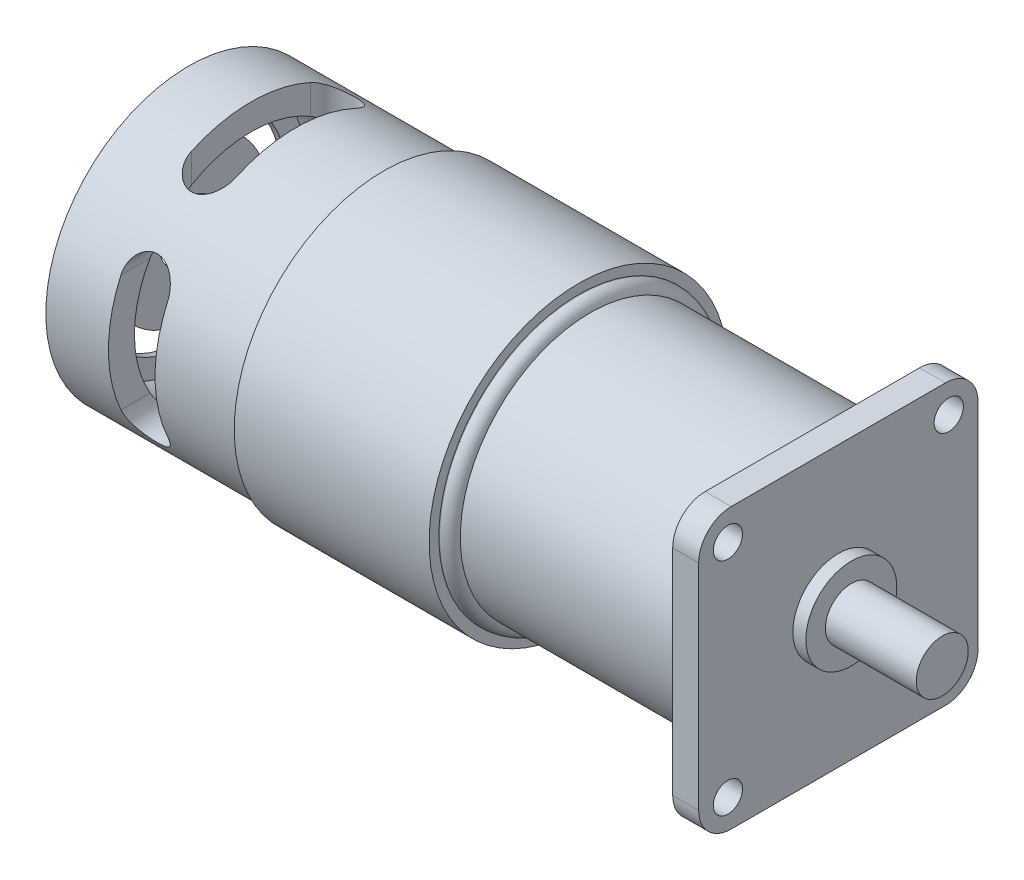
SolidWorks part; units mm, degrees
ref_plane "前视基准面" through (0, 0, 0) normal (0, 0, 1) x (1, 0, 0)
ref_plane "上视基准面" through (0, 0, 0) normal (0, 1, 0) x (1, 0, 0)
ref_plane "右视基准面" through (0, 0, 0) normal (1, 0, 0) x (0, 0, -1)
sketch "草图1" plane through (0, 0, 0) normal (0, 0, 1) x (1, 0, 0)
  line L7 (96, 20) -> (60, 20)
  line L8 (60, 20) -> (60, 23)
  line L9 (60, 23) -> (30, 23)
  line L10 (30, 23) -> (30, 22)
  line L11 (30, 22) -> (0, 22)
  line L12 (0, 22) -> (0, 0)
  line L13 (96, 20) -> (96, 0)
  line L14 (96, 0) -> (0, 0)
  dimension "D1" = 30
  dimension "D2" = 1
  dimension "D3" = 20
  dimension "D4" = 30
  dimension "D5" = 3
  dimension "D6" = 96
revolve "旋转1" add sketch "草图1" angle 360 about L14
sketch "草图2" plane through (0, 0, 0) normal (0, 0, 1) x (1, 0, 0)
  line L0 (96, 0) -> (96, 7)
  line L1 (96, -20) -> (96, 20) construction
  line L2 (96, 7) -> (102, 7)
  line L3 (102, 7) -> (102, 4)
  line L4 (102, 4) -> (116, 4)
  line L5 (116, 4) -> (116, 0)
  line L6 (116, 0) -> (96, 0)
  dimension "D1" = 6
  dimension "D2" = 20
  dimension "D3" = 7
  dimension "D4" = 4
revolve "旋转2" add sketch "草图2" angle 360 about L6
sketch "草图11" plane through (96, 0, 0) normal (1, 0, 0) x (0, 0, -1)
  line L1 (-21.5, 21.5) -> (21.5, 21.5)
  line L2 (-21.5, 21.5) -> (-21.5, -21.5)
  line L3 (-21.5, -21.5) -> (21.5, -21.5)
  line L4 (21.5, 21.5) -> (21.5, -21.5)
  line L5 (-21.5, 21.5) -> (21.5, -21.5) construction
  line L6 (-21.5, -21.5) -> (21.5, 21.5) construction
  point P0 (0, 0)
  dimension "D1" = 43
  dimension "D2" = 43
extrude "凸台-拉伸4" add sketch "草图11" along normal blind 4 separate body
sketch "草图12" plane through (0, 0, 0) normal (-1, 0, 0) x (0, 0, 1)
  circle A0 centre (0, 0) radius 18
  dimension "D1" = 36
extrude "切除-拉伸1" cut sketch "草图12" against normal blind 60
sketch "草图13" plane through (60, 0, 0) normal (-1, 0, 0) x (0, 0, 1)
  circle A0 centre (0, 0) radius 4
  dimension "D1" = 8
extrude "凸台-拉伸5" add sketch "草图13" along normal blind 62
sketch "草图14" plane through (0, 0, 0) normal (-1, 0, 0) x (0, 0, 1)
  circle A0 centre (0, 0) radius 20
  dimension "D1" = 40
extrude "凸台-拉伸6" add sketch "草图14" along normal blind 1
fillet "圆角1" radius 0.5 1 edges at (-1, 0, 20)
ref_axis "基准轴1" through (-29.822, 0, 0) along (1, 0, 0)
sketch "草图17" plane through (-1, 0, 0) normal (-1, 0, 0) x (0, 0, 1)
  arc A0 (-13.4771, 0) -> (0, 13.4771) centre (0, 0) cw construction
  arc A1 (0, 15.0897) -> (-15.0897, 0) centre (0, 0) ccw
  arc A2 (0, 11.8644) -> (-11.8644, 0) centre (0, 0) ccw
  arc A3 (0, 11.8644) -> (0, 15.0897) centre (0, 13.4771) ccw
  arc A4 (-15.0897, 0) -> (-11.8644, 0) centre (-13.4771, 0) ccw
  arc A5 (13.4771, 0) -> (0, -13.4771) centre (0, 0) cw construction
  arc A6 (0, -15.0897) -> (15.0897, 0) centre (0, 0) ccw
  arc A7 (0, -11.8644) -> (11.8644, 0) centre (0, 0) ccw
  arc A8 (0, -11.8644) -> (0, -15.0897) centre (0, -13.4771) ccw
  arc A9 (15.0897, 0) -> (11.8644, 0) centre (13.4771, 0) ccw
  point P4 (-9.5297, 9.5297)
  point P14 (9.5297, -9.5297)
  point P19 (0, 0)
  dimension "D1" = 2
extrude "切除-拉伸6" cut sketch "草图17" against normal blind 10
sketch "草图19" plane through (-2, 0, 0) normal (-1, 0, 0) x (0, 0, 1)
  circle A0 centre (0, 0) radius 1.7291
extrude "凸台-拉伸9" add sketch "草图19" along normal blind 2
fillet "圆角2" radius 1.7 1 edges at (-4, 0, 1.7291)
sketch "草图20" plane through (-1, 0, 0) normal (-1, 0, 0) x (0, 0, 1)
  circle A0 centre (0, 0) radius 4.5
  dimension "D1" = 9
extrude "切除-拉伸9" cut sketch "草图20" against normal blind 2
sketch "草图21" plane through (60, 0, 0) normal (1, 0, 0) x (0, 0, -1)
  circle A0 centre (0, 0) radius 21.5
  dimension "D1" = 43
extrude "凸台-拉伸10" add sketch "草图21" along normal blind 1.8
fillet "圆角3" radius 1.7 1 edges at (61.8, 0, -21.5)
sketch "草图24"
ref_plane "基准面1" through (0, 0, 0) normal (0, 0, -1) x (1, 0, 0)
ref_plane "基准面2" through (0, 0, 22) normal (0, 0, 1) x (1, 0, 0)
sketch "草图45" plane through (0, 0, 0) normal (0, 0, -1) x (1, 0, 0)
  line L0 (13.2288, -8.995) -> (13.2288, 8.995) construction
  line L1 (9.6389, -8.995) -> (9.6389, 8.995)
  line L2 (16.8187, -8.995) -> (16.8187, 8.995)
  arc A0 (9.6389, -8.995) -> (16.8187, -8.995) centre (13.2288, -8.995) ccw
  arc A1 (16.8187, 8.995) -> (9.6389, 8.995) centre (13.2288, 8.995) ccw
  point P2 (13.2288, 0)
extrude "切除-拉伸10" cut sketch "草图45" against normal through all both and the other way through all
ref_plane "基准面3" through (0, 22, 0) normal (0, 1, 0) x (1, 0, 0)
sketch "草图46" plane through (0, 22, 0) normal (0, 1, 0) x (1, 0, 0)
  line L0 (13.0327, -9.1644) -> (13.0327, 9.1644) construction
  line L1 (23.1, 0) -> (-23.1, 0) construction
  line L2 (9.5875, -9.1644) -> (9.5875, 9.1644)
  line L3 (16.478, -9.1644) -> (16.478, 9.1644)
  arc A0 (9.5875, -9.1644) -> (16.478, -9.1644) centre (13.0327, -9.1644) ccw
  arc A1 (16.478, 9.1644) -> (9.5875, 9.1644) centre (13.0327, 9.1644) ccw
  point P4 (13.0327, 0)
extrude "切除-拉伸11" cut sketch "草图46" against normal through all both and the other way through all
sketch "草图48" plane through (16.8187, 0, 0) normal (-1, 0, 0) x (0, 0, 1)
  circle A0 centre (0, 0) radius 4
extrude "凸台-拉伸11" add sketch "草图48" along normal blind 18.5
sketch "草图49" plane through (100, 0, 0) normal (1, 0, 0) x (0, 0, -1)
  line L0 (21.5, 21.5) -> (-21.5, 21.5) construction
  line L1 (-21.5, 21.5) -> (-21.5, -21.5) construction
  circle A0 centre (-17, 17) radius 2.25
  dimension "D1" = 4.5
  dimension "D2" = 4.5
  dimension "D3" = 4.5
extrude "切除-拉伸12" cut sketch "草图49" against normal blind 18.5
mirror "镜向1" about plane through (0, 0, 0) normal (0, 0, -1) of "切除-拉伸12"
sketch "草图50" plane through (100, 0, 0) normal (1, 0, 0) x (0, 0, -1)
  line L0 (21.5, -21.5) -> (21.5, 21.5) construction
  line L3 (-21.5, -21.5) -> (21.5, -21.5) construction
  circle A0 centre (17, -17) radius 2.25
  dimension "D1" = 4.5
  dimension "D2" = 4.5
  dimension "D3" = 4.5
extrude "切除-拉伸13" cut sketch "草图50" against normal blind 18.5 contours A0
mirror "镜向2" about plane through (0, 0, 0) normal (0, 0, -1) of "切除-拉伸13"
fillet "圆角4" radius 5 4 edges at (98, 21.5, 21.5) (98, -21.5, 21.5) (98, -21.5, -21.5) (98, 21.5, -21.5)
